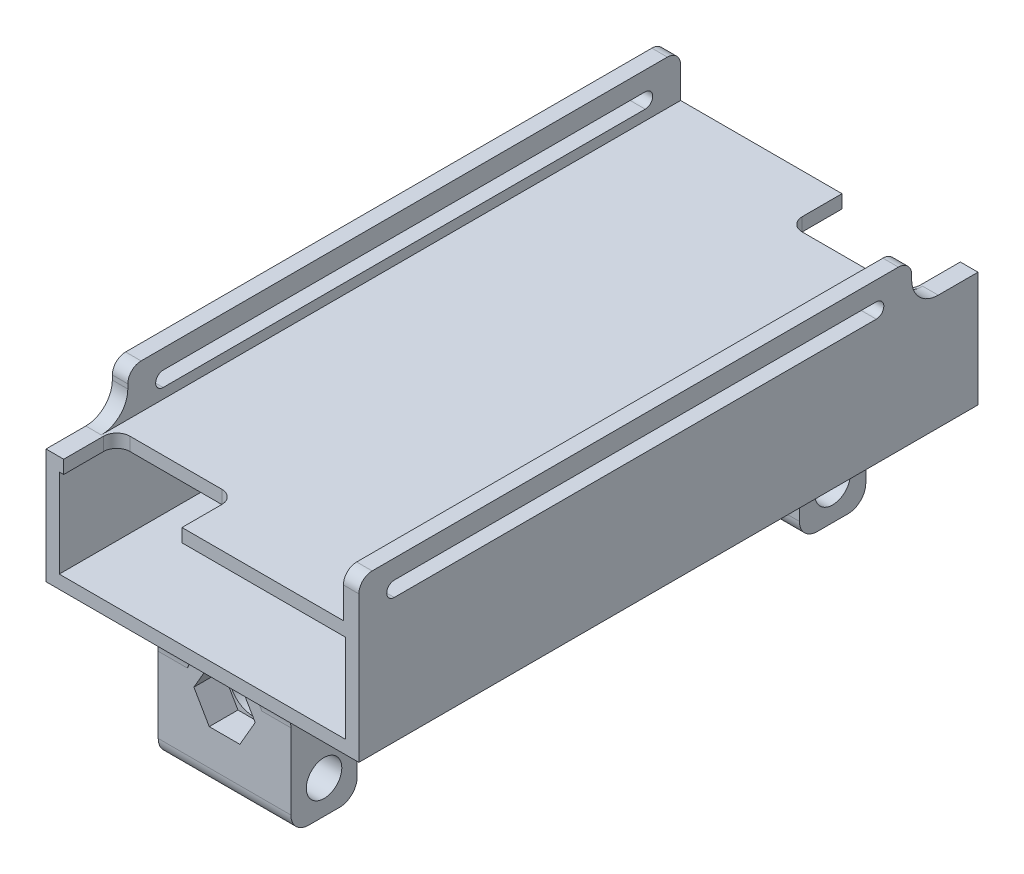
SolidWorks part; units mm, degrees
note: '?' marks a value the reader was unsure of.
ref_plane "Front Plane" through (0, 0, 0) normal (0, 0, 1) x (1, 0, 0)
ref_plane "Top Plane" through (0, 0, 0) normal (0, 1, 0) x (1, 0, 0)
ref_plane "Right Plane" through (0, 0, 0) normal (1, 0, 0) x (0, 0, -1)
sketch "Sketch1" plane through (0, 0, 0) normal (0, 0, 1) x (1, 0, 0)
  line L1 (-32.375, 10) -> (32.375, 10)
  line L2 (-32.375, 10) -> (-32.375, -10)
  line L3 (-32.375, -10) -> (32.375, -10)
  line L4 (32.375, 10) -> (32.375, -10)
  line L5 (-32.375, 10) -> (32.375, -10) construction
  line L6 (-32.375, -10) -> (32.375, 10) construction
  point P0 (0, 0)
  dimension "D1" = 64.75
  dimension "D2" = 20
extrude "Body" add sketch "Sketch1" along normal blind 140
shell "Shell1" thickness 3
sketch "Sketch2" plane through (0, 13, 0) normal (0, 1, 0) x (1, 0, 0)
  line L0 (-35.375, -140) -> (-35.375, 0) construction
  line L1 (4.625, 0) -> (31.375, 0)
  line L2 (4.625, 0) -> (4.625, -12)
  line L3 (4.625, -12) -> (31.375, -12)
  line L4 (31.375, 0) -> (31.375, -12)
  line L5 (-31.375, -140) -> (-4.625, -140)
  line L6 (-31.375, -140) -> (-31.375, -128)
  line L7 (-31.375, -128) -> (-4.625, -128)
  line L8 (-4.625, -140) -> (-4.625, -128)
  line L9 (35.375, -140) -> (35.375, 0) construction
  line L10 (35.375, -140) -> (-35.375, -140) construction
  line L11 (35.375, 0) -> (-35.375, 0) construction
  dimension "D1" = 12
  dimension "D2" = 40
  dimension "D3" = 40
  dimension "D4" = 4
  dimension "D5" = 4
extrude "Switch_cutout" cut sketch "Sketch2" against normal up to next
ref_plane "Plane1" through (0, 0, 0) normal (-1, 0, 0) x (0, 0, 1)
sketch "Sketch4" plane through (0, 0, 0) normal (-1, 0, 0) x (0, 0, 1)
  line L0 (70, -19.8206) -> (70, -43.8873) construction
  line L1 (5, -13) -> (20, -13)
  line L2 (5, -13) -> (5, -40)
  line L3 (5, -40) -> (20, -40)
  line L4 (20, -13) -> (20, -40)
  line L9 (140, 13) -> (0, 13) construction
  line L10 (140, -13) -> (0, -13) construction
  line L11 (135, -40) -> (120, -40)
  line L12 (120, -13) -> (120, -40)
  line L13 (135, -13) -> (135, -40)
  line L14 (135, -13) -> (120, -13)
  line L15 (0, 13) -> (0, -13) construction
  circle A1 centre (12.5, -32.5) radius 4.0125
  circle A2 centre (127.5, -32.5) radius 4.0125
  point P16 (12.5, -40)
  point P17 (70, 13)
  dimension "D1" = 8.025
  dimension "D2" = 15
  dimension "D3" = 27
  dimension "D4" = 7.5
  dimension "D5" = 5
extrude "Axle_holder" add sketch "Sketch4" along normal mid plane 30
sketch "Sketch5" plane through (0, 0, 0) normal (-1, 0, 0) x (0, 0, 1)
  circle A0 centre (12.5, -32.5) radius 2.5
  circle A1 centre (127.5, -32.5) radius 2.5
  circle A2 centre (12.5, -32.5) radius 4.0125 construction
  circle A4 centre (12.5, -32.5) radius 4.0125
  circle A5 centre (127.5, -32.5) radius 4.0125
  circle A7 centre (127.5, -32.5) radius 4.0125 construction
  dimension "D1" = 5
extrude "Bushing_holder" add sketch "Sketch5" along normal mid plane 18
fillet "Fillet3" radius 4 4 edges at (0, -40, 5) (0, -40, 20) (0, -40, 135) (0, -40, 120)
fillet "Fillet4" radius 6 4 edges at (0, -13, 20) (0, -13, 135) (0, -13, 5) (0, -13, 120)
sketch "Sketch6" plane through (35.375, 0, 0) normal (1, 0, 0) x (0, 0, -1)
  line L0 (-132, 17) -> (-23, 17) construction
  line L1 (-140, 13) -> (-15, 13)
  line L2 (-140, 13) -> (-140, 23)
  line L3 (-140, 23) -> (-15, 23)
  line L4 (-15, 13) -> (-15, 23)
  line L5 (-132, 18.7) -> (-23, 18.7)
  line L6 (-132, 15.3) -> (-23, 15.3)
  line L7 (-140, -13) -> (-140, 13) construction
  line L8 (0, -13) -> (0, 13) construction
  line L9 (-140, 13) -> (0, 13) construction
  arc A0 (-132, 18.7) -> (-132, 15.3) centre (-132, 17) ccw
  arc A1 (-23, 15.3) -> (-23, 18.7) centre (-23, 17) ccw
  point P5 (-77.5, 17)
  dimension "D2" = 1.7
  dimension "D1" = 10
  dimension "D3" = 8
  dimension "D4" = 8
  dimension "D5" = 4
  dimension "D6" = 15
extrude "Slide_mount" add sketch "Sketch6" against normal blind 3.5
ref_plane "Plane2" through (0, 0, 0) normal (1, 0, 0) x (0, 0, -1)
ref_plane "Plane3" through (0, 0, 70) normal (0, 0, 1) x (1, 0, 0)
ref_axis "Axis1" through (0, -14.8, 70) along (0, 1, 0)?
pattern_circular "CirPattern1" count 2 over 360 about axis through (0, 0, 70) along (0, 1, 0) of "Slide_mount"
fillet "Fillet6" radius 3 4 edges at (33.625, 23, 140) (33.625, 23, 15) (-33.625, 23, 0) (-33.625, 23, 125)
fillet "Fillet7" radius 3 4 edges at (31.375, 11.5, 12) (4.625, 11.5, 12) (-4.625, 11.5, 128) (-31.375, 11.5, 128)
fillet "Fillet8" radius 6 2 edges at (33.625, 13, 15) (-33.625, 13, 125)
sketch "Sketch7" plane through (0, 0, 135) normal (0, 0, 1) x (1, 0, 0)
  line L1 (15, -18.9161) -> (-15, -18.9161) construction
  circle A0 centre (0, -21.9161) radius 5.5
  point P6 (0, -18.9161)
  dimension "D1" = 11
  dimension "D2" = 3
extrude "Cut-Extrude1" cut sketch "Sketch7" against normal up to next
sketch "Sketch8" plane through (0, 0, 135) normal (0, 0, 1) x (1, 0, 0)
  line L0 (-15, -13) -> (15, -13) construction
  circle A0 centre (0, -21.9161) radius 8.9161
  arc A1 (-4.6098, -18.9161) -> (4.6098, -18.9161) centre (0, -21.9161) ccw construction
extrude "Cut-Extrude2" cut sketch "Sketch8" along normal blind 9
sketch "Sketch9" plane through (0, 0, 120) normal (0, 0, -1) x (-1, 0, 0)
  line L1 (-9.815, -21.9161) -> (-4.9075, -30.4161)
  line L2 (-4.9075, -30.4161) -> (4.9075, -30.4161)
  line L3 (4.9075, -30.4161) -> (9.815, -21.9161)
  line L4 (9.815, -21.9161) -> (4.9075, -13.4161)
  line L5 (4.9075, -13.4161) -> (-4.9075, -13.4161)
  line L6 (-4.9075, -13.4161) -> (-9.815, -21.9161)
  circle A0 centre (0, -21.9161) radius 8.5 construction
  arc A1 (-4.6633, -19) -> (4.6633, -19) centre (0, -21.9161) ccw construction
  dimension "D1" = 17
extrude "Cut-Extrude3" cut sketch "Sketch9" against normal mid plane 7
sketch "Sketch10" plane through (0, 0, 135) normal (0, 0, 1) x (1, 0, 0)
  line L1 (3.4641, -15.9161) -> (-3.4641, -15.9161)
  line L2 (-3.4641, -15.9161) -> (-6.9282, -21.9161)
  line L3 (-6.9282, -21.9161) -> (-3.4641, -27.9161)
  line L4 (-3.4641, -27.9161) -> (3.4641, -27.9161)
  line L5 (3.4641, -27.9161) -> (6.9282, -21.9161)
  line L6 (6.9282, -21.9161) -> (3.4641, -15.9161)
  circle A0 centre (0, -21.9161) radius 6 construction
  circle A1 centre (0, -21.9161) radius 5.5 construction
  dimension "D1" = 12
extrude "Cut-Extrude4" cut sketch "Sketch10" against normal blind 6.5
